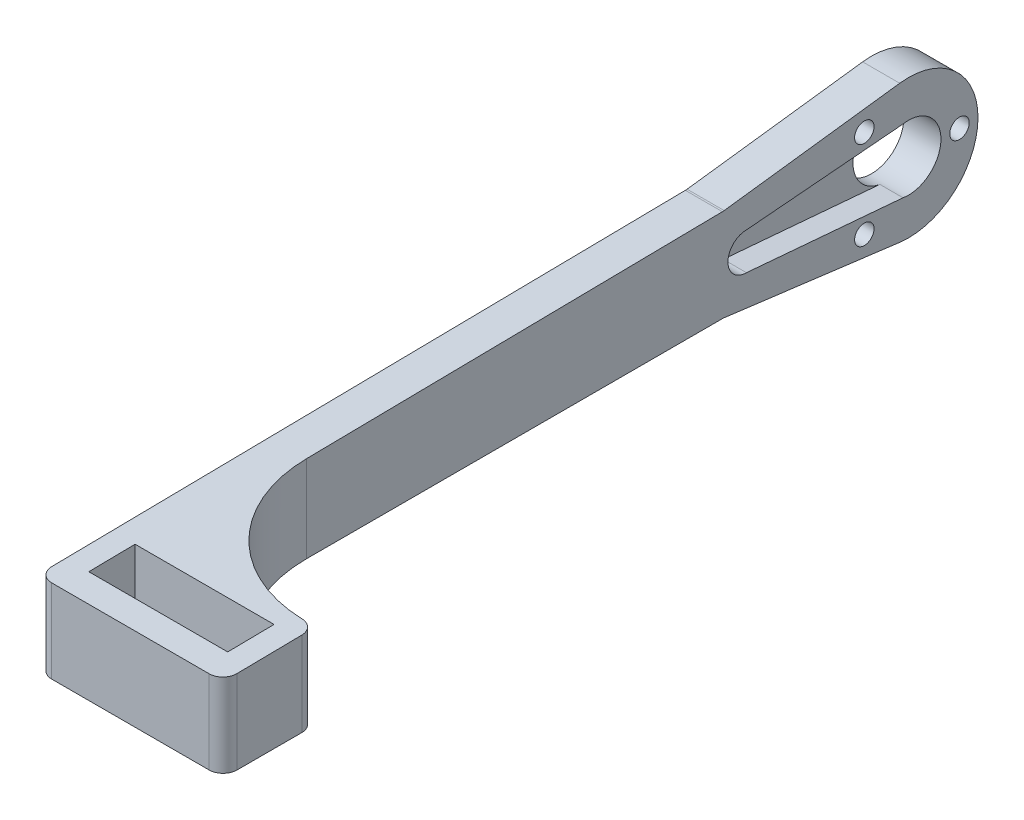
SolidWorks part; units mm, degrees
ref_plane "Plan de face" through (0, 0, 0) normal (0, 0, 1) x (1, 0, 0)
ref_plane "Plan de dessus" through (0, 0, 0) normal (0, 1, 0) x (1, 0, 0)
ref_plane "Plan de droite" through (0, 0, 0) normal (1, 0, 0) x (0, 0, -1)
sketch "Esquisse1" plane through (0, 0, 0) normal (1, 0, 0) x (0, 0, -1)
  line L0 (-47.7273, 0) -> (67.3318, 0) construction
  line L1 (-30, 5) -> (-30, -5)
  line L4 (0, 18.828) -> (0, -23.0645) construction
  line L7 (-30, 5) -> (30, 5)
  line L8 (-30, -5) -> (30, -5)
  line L9 (30, 12.9505) -> (30, -16.4973) construction
  line L10 (49.0473, 7.4392) -> (49.0473, -17.5453) construction
  line L11 (30, 5) -> (49.0473, 7.4392)
  line L12 (30, -5) -> (49.0473, -7.4392)
  line L13 (50, 0) -> (50, 7.5) construction
  circle A2 centre (-40, 0) radius 11.1803 construction
  arc A5 (49.0473, 7.4392) -> (49.0473, -7.4392) centre (50, 0) cw construction
  arc A8 (49.0473, -7.4392) -> (50, 7.5) centre (50, 0) ccw
  arc A9 (49.0473, 7.4392) -> (50, 7.5) centre (50, 0) cw
  point P20 (0, -5)
  point P22 (0, 5)
  dimension "D3" = 10
  dimension "D4" = 7.5
  dimension "D7" = 40
  dimension "D1" = 80
  dimension "D2" = 90
  dimension "D8" = 20
extrude "Boss.-Extru.1" add sketch "Esquisse1" along normal blind 4 contours L1 | L1 L8 L12 A8 A9 L11 L7 region at (0, 0, -15.8768)
sketch "Esquisse2" plane through (4, 0, 0) normal (1, 0, 0) x (0, 0, -1)
  line L2 (49.0473, 7.4392) -> (30, 5)
  line L8 (30, 5) -> (-30, 5)
  line L9 (30, 5) -> (-30, 5)
  line L10 (-30, -5) -> (30, -5)
  line L11 (-30, -5) -> (30, -5)
  line L14 (49.0473, 7.4392) -> (30, 5)
  line L16 (30, -5) -> (49.0473, -7.4392)
  line L17 (30, -5) -> (49.0473, -7.4392)
  line L19 (-30, 5) -> (-30, -5)
  line L20 (-30, 5) -> (-30, -5)
  arc A2 (49.0473, -7.4392) -> (49.0473, 7.4392) centre (50, 0) ccw
  circle A6 centre (50, 0) radius 3.5
  arc A17 (49.0473, -7.4392) -> (49.0473, 7.4392) centre (50, 0) ccw
  dimension "D3" = 7
  dimension "D1" = 0
extrude "Enlèv. mat.-Extru.1" cut sketch "Esquisse2" against normal blind 10 contours A6
sketch "Esquisse3" plane through (4, 0, 0) normal (1, 0, 0) x (0, 0, -1)
  line L0 (0, 0) -> (74.7488, 0) construction
  line L1 (38.1014, 11.1997) -> (38.1014, -12.7742) construction
  line L2 (49.0473, 7.4392) -> (30, 5)
  line L6 (23.0641, 3.5) -> (53.2637, 3.5) construction
  line L7 (0, 17.2639) -> (0, -16.0675) construction
  line L8 (30.5083, 6.6344) -> (30.5083, -6.2819) construction
  line L11 (32.5, 2) -> (50, 3.5)
  line L12 (32.5, -2) -> (50, -3.5)
  line L15 (30, 5) -> (-30, 5)
  line L16 (30, 5) -> (-30, 5)
  line L17 (-30, -5) -> (30, -5)
  line L18 (-30, -5) -> (30, -5)
  line L21 (49.0473, 7.4392) -> (30, 5)
  line L23 (30, -5) -> (49.0473, -7.4392)
  line L24 (30, -5) -> (49.0473, -7.4392)
  line L26 (-30, 5) -> (-30, -5)
  line L27 (-30, 5) -> (-30, -5)
  circle A0 centre (50, 0) radius 3.5 construction
  circle A1 centre (32.5, 0) radius 2 construction
  arc A2 (49.0473, -7.4392) -> (49.0473, 7.4392) centre (50, 0) ccw
  circle A3 centre (50, 0) radius 3.5 construction
  arc A6 (32.5, -2) -> (32.5, 2) centre (32.5, 0) cw
  arc A7 (50, -3.5) -> (50, 3.5) centre (50, 0) ccw
  circle A8 centre (50, 0) radius 3.5
  arc A18 (49.0473, -7.4392) -> (49.0473, 7.4392) centre (50, 0) ccw
  circle M28 centre (50, 0) radius 3.5
  dimension "D4" = 17.5
  dimension "D5" = 4
  dimension "D3" = 3.5
  dimension "D1" = 0
extrude "Enlèv. mat.-Extru.2" cut sketch "Esquisse3" against normal blind 2.5 contours A6 L12 L11 M28 region at (4, 0, -39.768)
sketch "Esquisse5" plane through (4, 0, 0) normal (1, 0, 0) x (0, 0, -1)
  line L0 (0, 16.8077) -> (0, -27.9422) construction
  line L1 (-64.0496, 0) -> (62.7771, 0) construction
  line L6 (50, 0) -> (34.0152, 15.9848) construction
  line L8 (49.0473, 7.4392) -> (30, 5)
  line L9 (30, 5) -> (-30, 5)
  line L10 (-30, -5) -> (30, -5)
  line L13 (30, 5) -> (-30, 5)
  line L14 (-30, -5) -> (30, -5)
  line L18 (49.0473, 7.4392) -> (30, 5)
  line L20 (30, -5) -> (49.0473, -7.4392)
  line L21 (30, -5) -> (49.0473, -7.4392)
  line L24 (-30, 5) -> (-30, -5)
  line L25 (-30, 5) -> (-30, -5)
  circle A2 centre (55.5, 0) radius 1.05
  arc A6 (49.0473, -7.4392) -> (49.0473, 7.4392) centre (50, 0) ccw
  circle A10 centre (50, 0) radius 6.75 construction
  circle A11 centre (45.227, 4.773) radius 1.05
  circle A12 centre (45.227, -4.773) radius 1.05
  arc A22 (49.0473, -7.4392) -> (49.0473, 7.4392) centre (50, 0) ccw
  dimension "D3" = 5.5
  dimension "D4" = 13.5
  dimension "D1" = 2.1
  dimension "D5" = 45
  dimension "D2" = 0
extrude "Enlèv. mat.-Extru.3" cut sketch "Esquisse5" against normal through all contours A2 | A11 | A12 region at (4, 0, -55.5)
sketch "Esquisse6" plane through (0, 0, 30) normal (0, 0, 1) x (1, 0, 0)
  line L0 (2, 5) -> (2, -5) construction
  line L1 (0, 5) -> (0, -5)
  line L4 (0, 5) -> (0, -5)
  line L5 (0, -5) -> (4, -5)
  line L6 (4, -5) -> (4, 5)
  line L7 (4, 5) -> (0, 5)
  line L9 (0, -5) -> (4, -5)
  line L10 (4, -5) -> (4, 5)
  line L11 (4, 5) -> (0, 5)
  line L12 (20, -5) -> (4, -5)
  line L13 (20, 5) -> (20, -5)
  line L14 (4, 5) -> (20, 5)
  line M9 (0, 5) -> (0, -5)
  line M10 (0, -5) -> (4, -5)
  line M11 (4, -5) -> (4, 5)
  line M12 (4, 5) -> (0, 5)
  dimension "D2" = 18
  dimension "D1" = 0
extrude "Boss.-Extru.2" add sketch "Esquisse6" along normal blind 10 contours L14 L12 L13 M11 | L0 L9 M12 M11 | L0 L11 M9 M10 | M9 region at (3, 0, 30) region at (1, 0, 30) region at (12, 0, 30)
sketch "Esquisse7" plane through (0, 5, 0) normal (0, 1, 0) x (1, 0, 0)
  line L0 (10, -40) -> (10, -30) construction
  line L1 (17.5, -37) -> (2.5, -37)
  line L2 (17.5, -37) -> (17.5, -32)
  line L3 (17.5, -32) -> (2.5, -32)
  line L4 (2.5, -37) -> (2.5, -32)
  line L5 (17.5, -37) -> (2.5, -32) construction
  line L6 (17.5, -32) -> (2.5, -37) construction
  line L8 (4, -30) -> (4, 30)
  line L9 (4, 30) -> (0, 30)
  line L10 (0, 30) -> (0, -40)
  line L11 (0, -40) -> (20, -40)
  line L12 (0, -40) -> (20, -40)
  line L13 (20, -40) -> (20, -30)
  line L14 (20, -40) -> (20, -30)
  line L15 (20, -30) -> (4, -30)
  line L16 (4, -30) -> (4, 30)
  line L18 (0, 30) -> (0, -40)
  line L29 (20, -30) -> (4, -30)
  line L32 (4, 30) -> (0, 30)
  point P2 (10, -34.5)
  dimension "D2" = 15
  dimension "D3" = 5
  dimension "D4" = 2
  dimension "D1" = 0
extrude "Enlèv. mat.-Extru.4" cut sketch "Esquisse7" against normal blind 10 contours L2 L1 L4 L3
fillet "Congé2" radius 1.5 5 edges at (2, 5, -30) (2, -5, -30) (20, 0, 30) (20, 0, 40) (0, 0, 40)
fillet "Congé3" radius 15 1 edges at (4, 0, 30)
sketch "Esquisse8" plane through (20, 0, 0) normal (1, 0, 0) x (0, 0, -1)
  line L0 (-40, 5) -> (-40, 4)
  line L1 (-40, 4) -> (29.9043, 5)
  line L2 (29.9043, 5) -> (-39.25, 5)
  line L3 (-38.5, 5) -> (-40, 5) construction
  line L4 (-38.5, 5) -> (-40, 5)
  line L5 (-40, 5) -> (-40, -5)
  line L6 (-40, -5) -> (-38.5, -5)
  line L7 (-38.5, -5) -> (-38.5, 5)
  line L8 (-38.5, 5) -> (-40, 5) construction
  line L9 (-40, 5) -> (-40, -5) construction
  line L10 (-40, -5) -> (-38.5, -5) construction
  line L11 (-38.5, -5) -> (-38.5, 5) construction
  line L12 (-38.5, -5) -> (-31.5, -5)
  line L13 (-31.5, -5) -> (-31.5, 5)
  line L14 (-31.5, 5) -> (-38.5, 5)
  line L15 (-38.5, 5) -> (-38.5, -5)
  line L16 (-38.5, -5) -> (-31.5, -5) construction
  line L17 (-31.5, -5) -> (-31.5, 5) construction
  line L18 (-31.5, 5) -> (-38.5, 5) construction
  line L19 (-38.5, 5) -> (-38.5, -5) construction
  line L20 (-31.5, -5) -> (-30.0007, -5)
  line L21 (-30.0007, -5) -> (-30.0007, 5)
  line L22 (-30.0007, 5) -> (-31.5, 5)
  line L23 (-31.5, 5) -> (-31.5, -5)
  line L24 (-31.5, -5) -> (-30.0007, -5) construction
  line L25 (-30.0007, -5) -> (-30.0007, 5) construction
  line L26 (-30.0007, 5) -> (-31.5, 5) construction
  line L27 (-31.5, 5) -> (-31.5, -5) construction
  line L28 (-15.0076, 5) -> (-30.0007, 5)
  line L29 (-30.0007, 5) -> (-30.0007, -5)
  line L30 (-30.0007, -5) -> (-15.0076, -5)
  line L31 (-15.0076, -5) -> (-15.0076, 5)
  line L32 (-15.0076, 5) -> (-30.0007, 5) construction
  line L33 (-30.0007, 5) -> (-30.0007, -5) construction
  line L34 (-30.0007, -5) -> (-15.0076, -5) construction
  line L35 (-15.0076, -5) -> (-15.0076, 5) construction
  line L36 (-39.25, 5) -> (-40, 5)
  line L37 (29.9043, 5) -> (-15.0076, 5)
  line L38 (-15.0076, 5) -> (-15.0076, -5)
  line L39 (-15.0076, -5) -> (29.9043, -5)
  line L40 (30.0949, -5.0122) -> (49.0473, -7.4392)
  line L41 (49.0473, 7.4392) -> (30.0949, 5.0122)
  line L42 (29.9043, 5) -> (-15.0076, 5) construction
  line L43 (-15.0076, 5) -> (-15.0076, -5) construction
  line L44 (-15.0076, -5) -> (29.9043, -5) construction
  line L45 (30.0949, -5.0122) -> (49.0473, -7.4392) construction
  line L46 (49.0473, 7.4392) -> (30.0949, 5.0122) construction
  line L47 (2.2, 0) -> (-2.2, 0) construction
  line L48 (29.9043, -5) -> (-39.25, -5)
  line L49 (-40, -4) -> (29.9043, -5)
  line L50 (-40, -5) -> (-40, -4)
  line L51 (-39.25, -5) -> (-40, -5)
  arc A7 (30.0949, -5.0122) -> (29.9043, -5) centre (29.9043, -6.5) ccw
  arc A8 (49.0473, -7.4392) -> (49.0473, 7.4392) centre (50, 0) ccw
  arc A13 (29.9043, 5) -> (30.0949, 5.0122) centre (29.9043, 6.5) ccw
  arc A14 (30.0949, -5.0122) -> (29.9043, -5) centre (29.9043, -6.5) ccw construction
  arc A15 (49.0473, -7.4392) -> (49.0473, 7.4392) centre (50, 0) ccw construction
  arc A20 (29.9043, 5) -> (30.0949, 5.0122) centre (29.9043, 6.5) ccw construction
  line M33 (-31.5, -5) -> (-31.5, 5)
  line M34 (-31.5, 5) -> (-38.5, 5)
  line M35 (-38.5, 5) -> (-38.5, -5)
  dimension "D6" = 8
  dimension "D1" = 0
  dimension "D2" = 0
  dimension "D3" = 0
  dimension "D4" = 0
  dimension "D5" = 0
extrude "Enlèv. mat.-Extru.5" cut sketch "Esquisse8" against normal through all and the other way through all contours L1 L2 M33 | L1 M35 M33 M34 | L36 L0 L1 L2 region at (20, 4.5353, 35.0629) region at (20, 4.5661, 30.7534)
